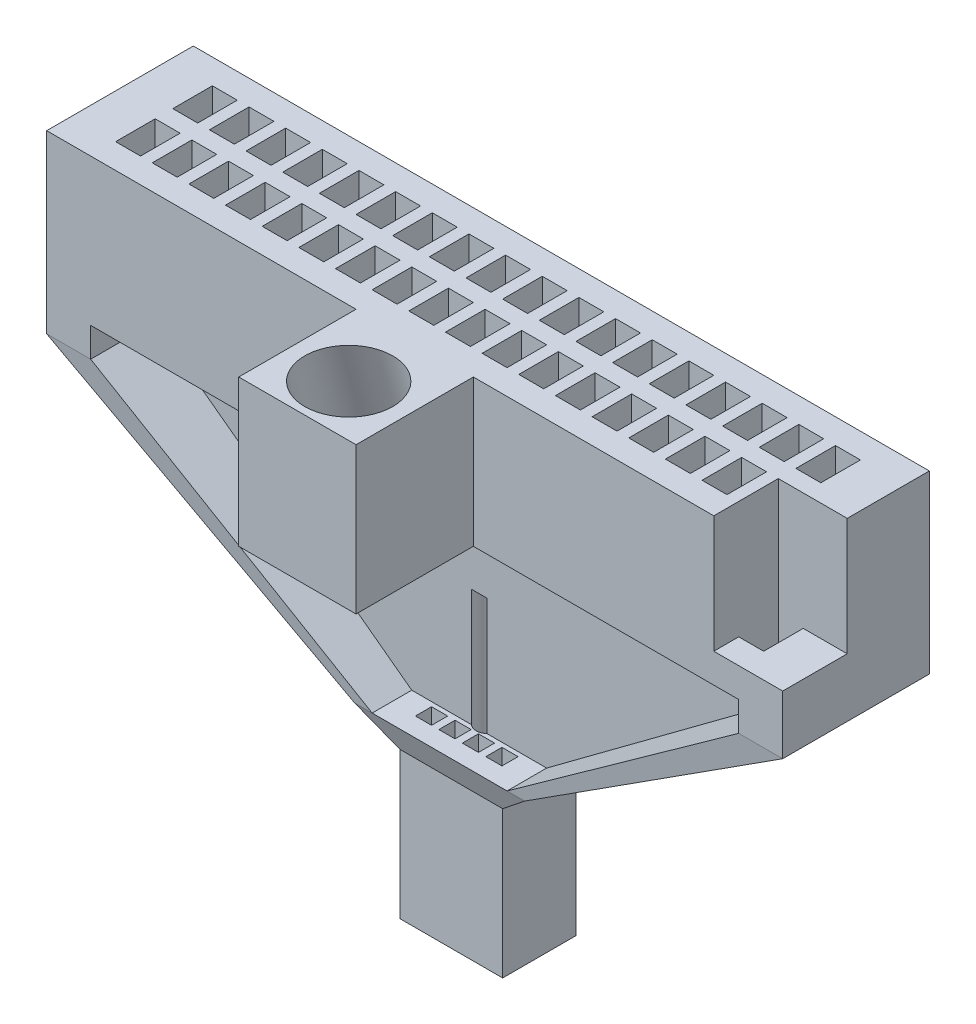
SolidWorks part; units mm, degrees
note: The reader was unsure of these and kept them because the rebuilt part matched: shared geometry of "Sketch13<3>".
ref_plane "Front Plane" through (0, 0, 0) normal (0, 0, 1) x (1, 0, 0)
ref_plane "Top Plane" through (0, 0, 0) normal (0, 1, 0) x (1, 0, 0)
ref_plane "Right Plane" through (0, 0, 0) normal (1, 0, 0) x (0, 0, -1)
sketch "main_block" plane through (0, 0, 0) normal (0, 1, 0) x (1, 0, 0)
  line L1 (-5.6188, 1.2192) -> (7.132, 1.2192)
  line L2 (-5.6188, 1.2192) -> (-5.6188, -1.3208)
  line L3 (-5.6188, -1.3208) -> (7.132, -1.3208)
  line L4 (7.132, 1.2192) -> (7.132, -1.3208)
  dimension "D1" = 12.7508
  dimension "D2" = 2.54
sketch "top_holes" plane through (0, 0, 0) normal (0, 1, 0) x (1, 0, 0)
  line L0 (7.132, 1.2192) -> (7.132, -1.3208) construction
  line L1 (6.37, 0.7874) -> (5.9382, 0.7874)
  line L2 (6.37, 0.7874) -> (6.37, 0.1016)
  line L3 (6.37, 0.1016) -> (5.9382, 0.1016)
  line L4 (5.9382, 0.7874) -> (5.9382, 0.1016)
  line L5 (-5.6188, 1.2192) -> (7.132, 1.2192) construction
  line L6 (5.3032, 0.7874) -> (5.3032, 0.1016)
  line L7 (5.735, 0.7874) -> (5.3032, 0.7874)
  line L8 (5.735, 0.7874) -> (5.735, 0.1016)
  line L9 (5.735, 0.1016) -> (5.3032, 0.1016)
  line L10 (4.6682, 0.7874) -> (4.6682, 0.1016)
  line L11 (5.1, 0.7874) -> (4.6682, 0.7874)
  line L12 (5.1, 0.7874) -> (5.1, 0.1016)
  line L13 (5.1, 0.1016) -> (4.6682, 0.1016)
  line L14 (4.0332, 0.7874) -> (4.0332, 0.1016)
  line L15 (4.465, 0.7874) -> (4.0332, 0.7874)
  line L16 (4.465, 0.7874) -> (4.465, 0.1016)
  line L17 (4.465, 0.1016) -> (4.0332, 0.1016)
  line L18 (3.3982, 0.7874) -> (3.3982, 0.1016)
  line L19 (3.83, 0.7874) -> (3.3982, 0.7874)
  line L20 (3.83, 0.7874) -> (3.83, 0.1016)
  line L21 (3.83, 0.1016) -> (3.3982, 0.1016)
  line L22 (2.7632, 0.7874) -> (2.7632, 0.1016)
  line L23 (3.195, 0.7874) -> (2.7632, 0.7874)
  line L24 (3.195, 0.7874) -> (3.195, 0.1016)
  line L25 (3.195, 0.1016) -> (2.7632, 0.1016)
  line L26 (2.1282, 0.7874) -> (2.1282, 0.1016)
  line L27 (2.56, 0.7874) -> (2.1282, 0.7874)
  line L28 (2.56, 0.7874) -> (2.56, 0.1016)
  line L29 (2.56, 0.1016) -> (2.1282, 0.1016)
  line L30 (1.4932, 0.7874) -> (1.4932, 0.1016)
  line L31 (1.925, 0.7874) -> (1.4932, 0.7874)
  line L32 (1.925, 0.7874) -> (1.925, 0.1016)
  line L33 (1.925, 0.1016) -> (1.4932, 0.1016)
  line L34 (0.8582, 0.7874) -> (0.8582, 0.1016)
  line L35 (1.29, 0.7874) -> (0.8582, 0.7874)
  line L36 (1.29, 0.7874) -> (1.29, 0.1016)
  line L37 (1.29, 0.1016) -> (0.8582, 0.1016)
  line L38 (0.2232, 0.7874) -> (0.2232, 0.1016)
  line L39 (0.655, 0.7874) -> (0.2232, 0.7874)
  line L40 (0.655, 0.7874) -> (0.655, 0.1016)
  line L41 (0.655, 0.1016) -> (0.2232, 0.1016)
  line L42 (-0.4117, 0.7874) -> (-0.4117, 0.1016)
  line L43 (0.0201, 0.7874) -> (-0.4117, 0.7874)
  line L44 (0.0201, 0.7874) -> (0.0201, 0.1016)
  line L45 (0.0201, 0.1016) -> (-0.4117, 0.1016)
  line L46 (-1.0467, 0.7874) -> (-1.0467, 0.1016)
  line L47 (-0.6149, 0.7874) -> (-1.0467, 0.7874)
  line L48 (-0.6149, 0.7874) -> (-0.6149, 0.1016)
  line L49 (-0.6149, 0.1016) -> (-1.0467, 0.1016)
  line L50 (-1.6817, 0.7874) -> (-1.6817, 0.1016)
  line L51 (-1.2499, 0.7874) -> (-1.6817, 0.7874)
  line L52 (-1.2499, 0.7874) -> (-1.2499, 0.1016)
  line L53 (-1.2499, 0.1016) -> (-1.6817, 0.1016)
  line L54 (-2.3167, 0.7874) -> (-2.3167, 0.1016)
  line L55 (-1.8849, 0.7874) -> (-2.3167, 0.7874)
  line L56 (-1.8849, 0.7874) -> (-1.8849, 0.1016)
  line L57 (-1.8849, 0.1016) -> (-2.3167, 0.1016)
  line L58 (-2.9517, 0.7874) -> (-2.9517, 0.1016)
  line L59 (-2.5199, 0.7874) -> (-2.9517, 0.7874)
  line L60 (-2.5199, 0.7874) -> (-2.5199, 0.1016)
  line L61 (-2.5199, 0.1016) -> (-2.9517, 0.1016)
  line L62 (-3.5867, 0.7874) -> (-3.5867, 0.1016)
  line L63 (-3.1549, 0.7874) -> (-3.5867, 0.7874)
  line L64 (-3.1549, 0.7874) -> (-3.1549, 0.1016)
  line L65 (-3.1549, 0.1016) -> (-3.5867, 0.1016)
  line L66 (-4.2217, 0.7874) -> (-4.2217, 0.1016)
  line L67 (-3.7899, 0.7874) -> (-4.2217, 0.7874)
  line L68 (-3.7899, 0.7874) -> (-3.7899, 0.1016)
  line L69 (-3.7899, 0.1016) -> (-4.2217, 0.1016)
  line L70 (-4.8567, 0.7874) -> (-4.8567, 0.1016)
  line L71 (-4.4249, 0.7874) -> (-4.8567, 0.7874)
  line L72 (-4.4249, 0.7874) -> (-4.4249, 0.1016)
  line L73 (-4.4249, 0.1016) -> (-4.8567, 0.1016)
  line L74 (5.3032, -0.2032) -> (5.3032, -0.889)
  line L75 (5.735, -0.2032) -> (5.3032, -0.2032)
  line L76 (5.735, -0.2032) -> (5.735, -0.889)
  line L77 (5.735, -0.889) -> (5.3032, -0.889)
  line L78 (4.6682, -0.2032) -> (4.6682, -0.889)
  line L79 (5.1, -0.2032) -> (4.6682, -0.2032)
  line L80 (5.1, -0.2032) -> (5.1, -0.889)
  line L81 (5.1, -0.889) -> (4.6682, -0.889)
  line L82 (4.0332, -0.2032) -> (4.0332, -0.889)
  line L83 (4.465, -0.2032) -> (4.0332, -0.2032)
  line L84 (4.465, -0.2032) -> (4.465, -0.889)
  line L85 (4.465, -0.889) -> (4.0332, -0.889)
  line L86 (3.3982, -0.2032) -> (3.3982, -0.889)
  line L87 (3.83, -0.2032) -> (3.3982, -0.2032)
  line L88 (3.83, -0.2032) -> (3.83, -0.889)
  line L89 (3.83, -0.889) -> (3.3982, -0.889)
  line L90 (2.7632, -0.2032) -> (2.7632, -0.889)
  line L91 (3.195, -0.2032) -> (2.7632, -0.2032)
  line L92 (3.195, -0.2032) -> (3.195, -0.889)
  line L93 (3.195, -0.889) -> (2.7632, -0.889)
  line L94 (2.1282, -0.2032) -> (2.1282, -0.889)
  line L95 (2.56, -0.2032) -> (2.1282, -0.2032)
  line L96 (2.56, -0.2032) -> (2.56, -0.889)
  line L97 (2.56, -0.889) -> (2.1282, -0.889)
  line L98 (1.4932, -0.2032) -> (1.4932, -0.889)
  line L99 (1.925, -0.2032) -> (1.4932, -0.2032)
  line L100 (1.925, -0.2032) -> (1.925, -0.889)
  line L101 (1.925, -0.889) -> (1.4932, -0.889)
  line L102 (0.8582, -0.2032) -> (0.8582, -0.889)
  line L103 (1.29, -0.2032) -> (0.8582, -0.2032)
  line L104 (1.29, -0.2032) -> (1.29, -0.889)
  line L105 (1.29, -0.889) -> (0.8582, -0.889)
  line L106 (0.2232, -0.2032) -> (0.2232, -0.889)
  line L107 (0.655, -0.2032) -> (0.2232, -0.2032)
  line L108 (0.655, -0.2032) -> (0.655, -0.889)
  line L109 (0.655, -0.889) -> (0.2232, -0.889)
  line L110 (-0.4117, -0.2032) -> (-0.4117, -0.889)
  line L111 (0.0201, -0.2032) -> (-0.4117, -0.2032)
  line L112 (0.0201, -0.2032) -> (0.0201, -0.889)
  line L113 (0.0201, -0.889) -> (-0.4117, -0.889)
  line L114 (-1.0467, -0.2032) -> (-1.0467, -0.889)
  line L115 (-0.6149, -0.2032) -> (-1.0467, -0.2032)
  line L116 (-0.6149, -0.2032) -> (-0.6149, -0.889)
  line L117 (-0.6149, -0.889) -> (-1.0467, -0.889)
  line L118 (-1.6817, -0.2032) -> (-1.6817, -0.889)
  line L119 (-1.2499, -0.2032) -> (-1.6817, -0.2032)
  line L120 (-1.2499, -0.2032) -> (-1.2499, -0.889)
  line L121 (-1.2499, -0.889) -> (-1.6817, -0.889)
  line L122 (-2.3167, -0.2032) -> (-2.3167, -0.889)
  line L123 (-1.8849, -0.2032) -> (-2.3167, -0.2032)
  line L124 (-1.8849, -0.2032) -> (-1.8849, -0.889)
  line L125 (-1.8849, -0.889) -> (-2.3167, -0.889)
  line L126 (-2.9517, -0.2032) -> (-2.9517, -0.889)
  line L127 (-2.5199, -0.2032) -> (-2.9517, -0.2032)
  line L128 (-2.5199, -0.2032) -> (-2.5199, -0.889)
  line L129 (-2.5199, -0.889) -> (-2.9517, -0.889)
  line L130 (-3.5867, -0.2032) -> (-3.5867, -0.889)
  line L131 (-3.1549, -0.2032) -> (-3.5867, -0.2032)
  line L132 (-3.1549, -0.2032) -> (-3.1549, -0.889)
  line L133 (-3.1549, -0.889) -> (-3.5867, -0.889)
  line L134 (-4.2217, -0.2032) -> (-4.2217, -0.889)
  line L135 (-3.7899, -0.2032) -> (-4.2217, -0.2032)
  line L136 (-3.7899, -0.2032) -> (-3.7899, -0.889)
  line L137 (-3.7899, -0.889) -> (-4.2217, -0.889)
  line L138 (-4.8567, -0.2032) -> (-4.8567, -0.889)
  line L139 (-4.4249, -0.2032) -> (-4.8567, -0.2032)
  line L140 (-4.4249, -0.2032) -> (-4.4249, -0.889)
  line L141 (-4.4249, -0.889) -> (-4.8567, -0.889)
  line L142 (5.9382, -0.2032) -> (5.9382, -0.889)
  line L143 (6.37, -0.2032) -> (5.9382, -0.2032)
  line L144 (6.37, -0.2032) -> (6.37, -0.889)
  line L145 (6.37, -0.889) -> (5.9382, -0.889)
  line L148 (-5.6188, 1.2192) -> (-5.6188, -1.3208) construction
  dimension "D1" = 0.4318
  dimension "D2" = 0.6858
  dimension "D3" = 0.762
  dimension "D4" = 0.4318
  dimension "D5" = 18
  dimension "D6" = 2
extrude "well_block" add sketch "main_block" against normal blind 2.54
extrude "omnetics_wells" cut sketch "top_holes" against normal blind 2.54
ref_plane "Plane1" through (0, -6.35, 0) normal (0, 1, 0) x (1, 0, 0)
sketch "Sketch4" plane through (0, -6.35, 0) normal (0, 1, 0) x (1, 0, 0)
  line L1 (1.9249, 0.889) -> (-0.4117, 0.889)
  line L2 (1.9249, 0.889) -> (1.9249, -0.889)
  line L3 (1.9249, -0.889) -> (-0.4117, -0.889)
  line L4 (-0.4117, 0.889) -> (-0.4117, -0.889)
  line L5 (1.9249, 0.889) -> (-0.4117, -0.889) construction
  line L6 (1.9249, -0.889) -> (-0.4117, 0.889) construction
  point P0 (0.7566, 0)
  dimension "D1" = 2.3367
  dimension "D2" = 1.778
sketch "Sketch5" plane through (0, -2.54, 0) normal (0, -1, 0) x (1, 0, 0)
  line L1 (-4.8567, 0.2032) -> (6.37, 0.2032)
  line L2 (-4.8567, 0.2032) -> (-4.8567, -0.1016)
  line L3 (-4.8567, -0.1016) -> (6.37, -0.1016)
  line L4 (6.37, 0.2032) -> (6.37, -0.1016)
sketch "Sketch6" plane through (0, -6.35, 0) normal (0, 1, 0) x (1, 0, 0)
  line L1 (-0.4117, 0.1016) -> (1.925, 0.1016)
  line L2 (-0.4117, 0.1016) -> (-0.4117, -0.2032)
  line L3 (-0.4117, -0.2032) -> (1.925, -0.2032)
  line L4 (1.925, 0.1016) -> (1.925, -0.2032)
sketch "Sketch7" plane through (0, -6.35, 0) normal (0, 1, 0) x (1, 0, 0)
  line L0 (-0.4117, -0.889) -> (-0.4117, 0.889)
  line L1 (-0.4117, -0.889) -> (-0.7165, -0.889)
  line L2 (-0.4117, 0.889) -> (-0.7165, 0.889)
  line L3 (-0.7165, -0.889) -> (-0.7165, 0.889)
  dimension "D1" = 0.3048
sketch "Sketch8" plane through (0, -2.54, 0) normal (0, -1, 0) x (1, 0, 0)
  line L0 (-4.8567, 1.3208) -> (-4.8567, -1.2192)
  line L1 (-4.8567, 1.3208) -> (-5.6187, 1.3208)
  line L2 (-4.8567, -1.2192) -> (-5.6187, -1.2192)
  line L3 (-5.6187, 1.3208) -> (-5.6187, -1.2192)
  line L4 (-5.6188, 1.3208) -> (7.132, 1.3208) construction
  line L5 (7.132, -1.2192) -> (-5.6188, -1.2192) construction
  dimension "D1" = 0.762
  dimension "D2" = 0
  dimension "D3" = 0
extrude "supportbeam1" add sketch "Sketch8" along normal blind 0.508
sketch "Sketch9" plane through (0, -6.35, 0) normal (0, 1, 0) x (1, 0, 0)
  line L0 (1.925, -0.889) -> (1.9249, 0.889)
  line L1 (1.925, -0.889) -> (2.2298, -0.889)
  line L2 (1.9249, 0.889) -> (2.2297, 0.889)
  line L3 (2.2298, -0.889) -> (2.2297, 0.889)
  dimension "D1" = 0.3048
sketch "Sketch10" plane through (0, -2.54, 0) normal (0, -1, 0) x (1, 0, 0)
  line L0 (6.37, -1.2192) -> (6.37, 1.3208)
  line L1 (6.37, -1.2192) -> (7.132, -1.2192)
  line L2 (6.37, 1.3208) -> (7.132, 1.3208)
  line L3 (7.132, -1.2192) -> (7.132, 1.3208)
  line L4 (-5.6188, 1.3208) -> (-5.6187, 1.3208) construction
  line L5 (7.132, -1.2192) -> (-4.8567, -1.2192) construction
  dimension "D1" = 0.762
  dimension "D2" = 0
  dimension "D3" = 0
extrude "supportbeam2" add sketch "Sketch10" along normal blind 0.508
loft "arm1" add profiles "Sketch9" section "Sketch9" section face at (6.751, -3.048, 0.0508) connector at (1.925, -6.35, 0.889) connector at (6.37, -3.048, 1.3208)
loft "arm2" add profiles "Sketch7" section "Sketch7" section face at (-5.2377, -3.048, 0.0508) connector at (-0.4117, -6.35, 0.889) connector at (-4.8567, -3.048, 1.3208)
extrude "wall_divider" add sketch "Sketch5" along normal blind 0.508
loft "wall_divider2" add profiles "Sketch6" section face at (0.7566, -3.048, 0.0508) section "Sketch6" connector at (-4.8567, -3.048, -0.1016) connector at (-0.4117, -6.35, -0.1016)
sketch "Sketch12" plane through (0, -6.35, 0) normal (0, 1, 0) x (1, 0, 0)
  line L1 (-0.7165, 0.889) -> (2.2299, 0.889)
  line L2 (-0.7165, 0.889) -> (-0.7165, -0.889)
  line L3 (-0.7165, -0.889) -> (2.2299, -0.889)
  line L4 (2.2299, 0.889) -> (2.2299, -0.889)
  line L6 (-0.4117, 0.889) -> (-0.7165, 0.889) construction
  line L7 (-0.7165, -0.889) -> (-0.4117, -0.889) construction
  dimension "D1" = 0
  dimension "D2" = 2.9464
  dimension "D3" = 0
ref_plane "Plane2" through (0, -6.858, 0) normal (0, 1, 0) x (1, 0, 0)
sketch "Sketch13" plane through (0, -6.858, 0) normal (0, 1, 0) x (1, 0, 0)
  line L0 (0.8582, -0.2032) -> (0.8582, -0.889) construction
  line L1 (1.6456, 0.5842) -> (-0.1324, 0.5842)
  line L2 (1.6456, 0.5842) -> (1.6456, -0.6858)
  line L3 (1.6456, -0.6858) -> (-0.1324, -0.6858)
  line L4 (-0.1324, 0.5842) -> (-0.1324, -0.6858)
  line L5 (1.6456, 0.5842) -> (-0.1324, -0.6858) construction
  line L6 (1.6456, -0.6858) -> (-0.1324, 0.5842) construction
  line L7 (0.655, -0.889) -> (0.655, -0.2032) construction
  line L8 (6.37, -0.2032) -> (1.925, -0.2032) construction
  line L9 (1.925, 0.1016) -> (6.37, 0.1016) construction
  point P0 (0.7566, 0)
  dimension "D1" = 1.778
  dimension "D2" = 1.27
  dimension "D3" = 0.4826
  dimension "D4" = 0.7874
  dimension "D5" = 0.7874
  dimension "D6" = 0.4826
loft "exit_base" add profiles "Sketch12", "Sketch13" connector at (2.2299, -6.35, -0.889) connector at (1.6456, -6.858, -0.5842)
extrude "tetrode_funnel" add sketch "Sketch13<3>" against normal blind 2.54
sketch "Sketch13<3>" plane through (0, -6.858, 0) normal (0, 1, 0) x (1, 0, 0) same geometry as "Sketch13"
sketch "Sketch17" plane through (0, 0, 0) normal (0, 1, 0) x (1, 0, 0)
  line L1 (5.9382, -0.2032) -> (7.132, -0.2032)
  line L2 (5.9382, -0.2032) -> (5.9382, -1.3208)
  line L3 (5.9382, -1.3208) -> (7.132, -1.3208)
  line L4 (7.132, -0.2032) -> (7.132, -1.3208)
extrude "ground_wire_hole" cut sketch "Sketch17" against normal blind 2.032
sketch "Sketch19" plane through (0, -9.398, 0) normal (0, -1, 0) x (1, 0, 0)
  line L0 (-0.1324, -0.5842) -> (-0.1324, 0.6858) construction
  line L1 (-0.1324, 0.6858) -> (1.6456, 0.6858) construction
  circle A0 centre (0.7566, 0.0508) radius 0.2032
  point P2 (-0.1324, 0.0508)
  dimension "D1" = 0.889
  dimension "D2" = 0.635
extrude "fiber_optic_hole" cut sketch "Sketch19" against normal blind 5.08
sketch "Sketch20" plane through (0, 0, 1.3208) normal (0, 0, 1) x (1, 0, 0)
  line L0 (-4.8567, -2.54) -> (6.37, -2.54) construction
  line L1 (-0.2594, -2.54) -> (1.7726, -2.54)
  line L2 (-0.2594, -2.54) -> (-0.2594, 0)
  line L3 (-0.2594, 0) -> (1.7726, 0)
  line L4 (1.7726, -2.54) -> (1.7726, 0)
  line L5 (-5.6188, -2.54) -> (-5.6188, 0) construction
  line L6 (7.132, -2.032) -> (7.132, 0) construction
  dimension "D1" = 2.54
  dimension "D2" = 2.032
  dimension "D3" = 5.3594
  dimension "D4" = 5.3594
extrude "fiber_optic_holder" add sketch "Sketch20" along normal blind 2.032
sketch "Sketch24" plane through (0, -2.54, 0) normal (0, -1, 0) x (1, 0, 0)
  line L1 (-0.4117, 0.889) -> (1.925, 0.889) construction
  circle A0 centre (0.7606, 1.778) radius 0.762
  dimension "D1" = 0.889
sketch "Sketch25" plane through (0, 0, 0) normal (0, 1, 0) x (1, 0, 0)
  line L0 (1.7726, -3.3528) -> (-0.2594, -3.3528) construction
  circle A0 centre (0.7566, -2.4638) radius 0.762
  dimension "D1" = 0.889
loft "optic_holder_hole" cut profiles "Sketch24", "Sketch25" connector at (0.8724, -2.54, 2.5318) connector at (0.8398, 0, 3.2212)
sketch "tetrode_sketch" plane through (0, -9.398, 0) normal (0, -1, 0) x (1, 0, 0)
  line L0 (-0.1324, 0.6858) -> (1.6456, 0.6858) construction
  line L1 (1.5059, 0.5588) -> (1.2265, 0.5588)
  line L2 (1.5059, 0.5588) -> (1.5059, 0.2794)
  line L3 (1.5059, 0.2794) -> (1.2265, 0.2794)
  line L4 (1.2265, 0.5588) -> (1.2265, 0.2794)
  line L5 (1.6456, 0.6858) -> (1.6456, -0.5842) construction
  line L6 (1.0995, 0.5588) -> (0.8201, 0.5588)
  line L7 (1.0995, 0.5588) -> (1.0995, 0.2794)
  line L8 (1.0995, 0.2794) -> (0.8201, 0.2794)
  line L9 (0.8201, 0.5588) -> (0.8201, 0.2794)
  line L10 (0.6931, 0.5588) -> (0.4137, 0.5588)
  line L11 (0.6931, 0.5588) -> (0.6931, 0.2794)
  line L12 (0.6931, 0.2794) -> (0.4137, 0.2794)
  line L13 (0.4137, 0.5588) -> (0.4137, 0.2794)
  line L14 (0.2867, 0.5588) -> (0.0073, 0.5588)
  line L15 (0.2867, 0.5588) -> (0.2867, 0.2794)
  line L16 (0.2867, 0.2794) -> (0.0073, 0.2794)
  line L17 (0.0073, 0.5588) -> (0.0073, 0.2794)
  line L18 (1.5059, -0.1778) -> (1.2265, -0.1778)
  line L19 (1.5059, -0.1778) -> (1.5059, -0.4572)
  line L20 (1.5059, -0.4572) -> (1.2265, -0.4572)
  line L21 (1.2265, -0.1778) -> (1.2265, -0.4572)
  line L22 (1.0995, -0.1778) -> (0.8201, -0.1778)
  line L23 (1.0995, -0.1778) -> (1.0995, -0.4572)
  line L24 (1.0995, -0.4572) -> (0.8201, -0.4572)
  line L25 (0.8201, -0.1778) -> (0.8201, -0.4572)
  line L26 (0.6931, -0.1778) -> (0.4137, -0.1778)
  line L27 (0.6931, -0.1778) -> (0.6931, -0.4572)
  line L28 (0.6931, -0.4572) -> (0.4137, -0.4572)
  line L29 (0.4137, -0.1778) -> (0.4137, -0.4572)
  line L30 (0.2867, -0.1778) -> (0.0073, -0.1778)
  line L31 (0.2867, -0.1778) -> (0.2867, -0.4572)
  line L32 (0.2867, -0.4572) -> (0.0073, -0.4572)
  line L33 (0.0073, -0.1778) -> (0.0073, -0.4572)
  dimension "D1" = 0.2794
  dimension "D2" = 0.2794
  dimension "D3" = 0.127
  dimension "D4" = 0.1397
  dimension "D6" = 2
  dimension "D5" = 4
extrude "Cut-Extrude2" cut sketch "tetrode_sketch" against normal blind 3.302
